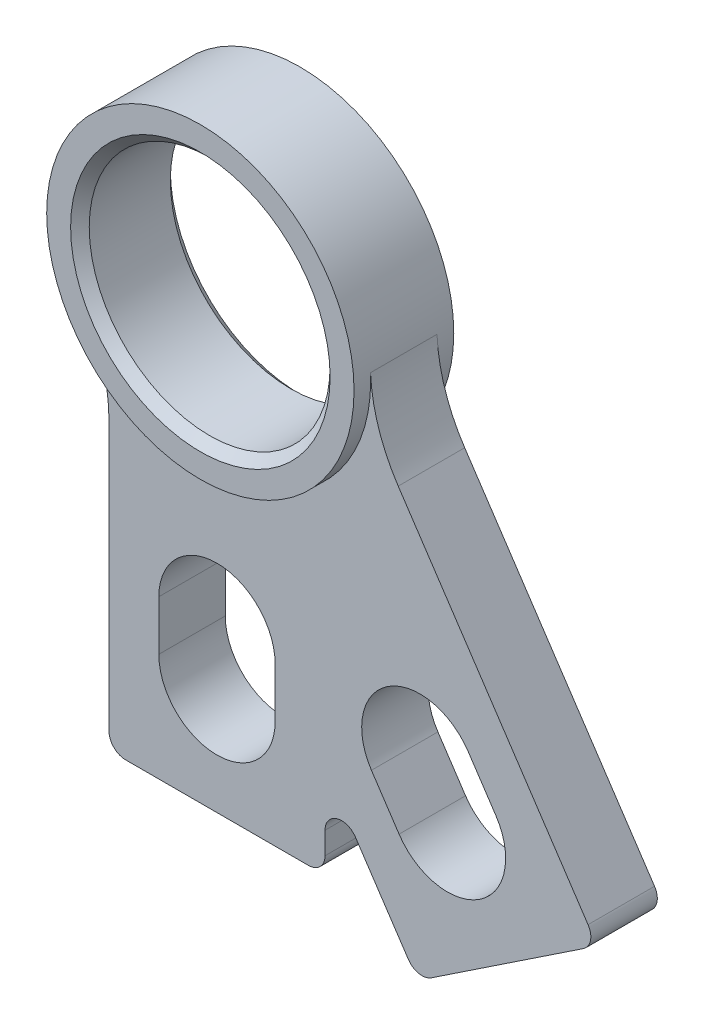
SolidWorks part; units mm, degrees
material "AISI 4130 Steel, annealed at 865C"
ref_plane "X-Y Datum" through (0, 0, 0) normal (0, 0, 1) x (1, 0, 0)
ref_plane "X-Z Datum" through (0, 0, 0) normal (0, 1, 0) x (1, 0, 0)
ref_plane "Y-Z Datum" through (0, 0, 0) normal (1, 0, 0) x (0, 0, -1)
sketch "Sketch1" plane through (0, 0, 0) normal (0, 0, 1) x (1, 0, 0)
  line L0 (0, -32.7206) -> (0, -27.9581) construction
  line L1 (-5.5562, -32.7206) -> (-5.5562, -27.9581)
  line L2 (5.5562, -32.7206) -> (5.5562, -27.9581)
  line L3 (22.0185, -33.0412) -> (19.3775, -29.078) construction
  line L4 (17.3948, -36.1224) -> (14.7538, -32.1592)
  line L5 (26.6421, -29.96) -> (24.0011, -25.9969)
  line L6 (-10.3187, -15.7343) -> (-10.3187, -43.0393)
  line L7 (-10.3187, -43.0393) -> (10.3187, -43.0393)
  line L10 (19.1539, -47.3502) -> (36.3275, -35.9058)
  line L11 (36.3275, -35.9058) -> (17.3122, -7.3712)
  line L12 (219.474, -329.3453) -> (0, 0) construction
  line L13 (0, -355.3502) -> (0, 0) construction
  line L14 (0, -38.2768) -> (0, -43.0393) construction
  line L15 (25.0997, -37.6648) -> (27.7407, -41.628) construction
  line L16 (25.3216, -27.9784) -> (29.2848, -25.3374) construction
  line L17 (-5.5562, -30.3393) -> (-10.3187, -30.3393) construction
  line L18 (-10.3187, -17.6393) -> (10.3187, -17.6393) construction
  line L19 (10.3187, -17.6393) -> (10.3187, -43.0393) construction
  line L20 (5.5562, -30.3393) -> (10.3187, -30.3393) construction
  line L21 (0, -22.4018) -> (0, -17.6393) construction
  line L22 (19.1539, -47.3502) -> (5.0685, -26.2134) construction
  line L23 (5.0685, -26.2134) -> (22.2421, -14.769) construction
  line L24 (16.0743, -34.1408) -> (12.1112, -36.7818) construction
  line L25 (16.2963, -24.4544) -> (13.6553, -20.4912) construction
  line L29 (0, -393.2916) -> (0, 0) construction
  line L30 (19.1539, -47.3502) -> (10.3187, -34.0921)
  line L31 (189.0102, -283.631) -> (-0.0704, 0.1056) construction
  line L32 (10.3187, -34.0921) -> (10.3187, -43.0393)
  circle A0 centre (0, 0) radius 11.5062
  arc A1 (-5.5562, -32.7206) -> (5.5562, -32.7206) centre (0, -32.7206) ccw
  arc A2 (5.5562, -27.9581) -> (-5.5562, -27.9581) centre (0, -27.9581) ccw
  arc A3 (17.3948, -36.1224) -> (26.6421, -29.96) centre (22.0185, -33.0412) ccw
  arc A4 (24.0011, -25.9969) -> (14.7538, -32.1592) centre (19.3775, -29.078) ccw
  arc A5 (14.6651, 0.6881) -> (-12.5852, -7.5598) centre (0, 0) ccw
  arc A6 (17.3122, -7.3712) -> (14.6651, 0.6881) centre (30.5226, 1.4322) cw
  arc A7 (-10.3187, -15.7343) -> (-12.5852, -7.5598) centre (-26.1937, -15.7343) ccw
  arc A14 (-12.5852, -7.5598) -> (14.6651, 0.6881) centre (0, 0) ccw
  point P5 (0, -30.3393)
  point P11 (20.698, -31.0596)
  point P24 (27.7407, -41.628)
  point P31 (0, -43.0393)
  point P39 (25.0997, -37.6648)
  dimension "D1" = 23.0124
  dimension "D2" = 3.175
  dimension "D8" = 15.875
  dimension "D3" = 20.6375
  dimension "D4" = 4.7625
  dimension "D5" = 25.4
  dimension "D6" = 8.89
  dimension "D7" = 1.905
extrude "Boss-Extrude2" add sketch "Sketch1" along normal mid plane 9.525 contours A5 A14 A0 region at (-4.1328, 13.6542, 0)
extrude "Boss-Extrude3" add sketch "Sketch1<4>" along normal mid plane 6.35 contours A14 A7 L6 L7 L10 L11 A6 A4 L5 A3 L4 A2 L2 A1 L1 region at (9.9882, -26.9444, 0)
sketch "Sketch1<4>" plane through (0, 0, 0) normal (0, 0, 1) x (1, 0, 0) same geometry as "Sketch1"
fillet "Fillet1" radius 1.5875 5 edges at (-10.3187, -43.0393, 0) (36.3275, -35.9058, 0) (10.3187, -43.0393, 0) (19.1539, -47.3502, 0) (10.3187, -34.0921, 0)
chamfer "Chamfer1" distance 0.889 angle 45 2 edges at (11.5062, 0, -4.7625) (11.5062, 0, 4.7625)
fillet "Fillet2" [suppressed] radius 1.27
